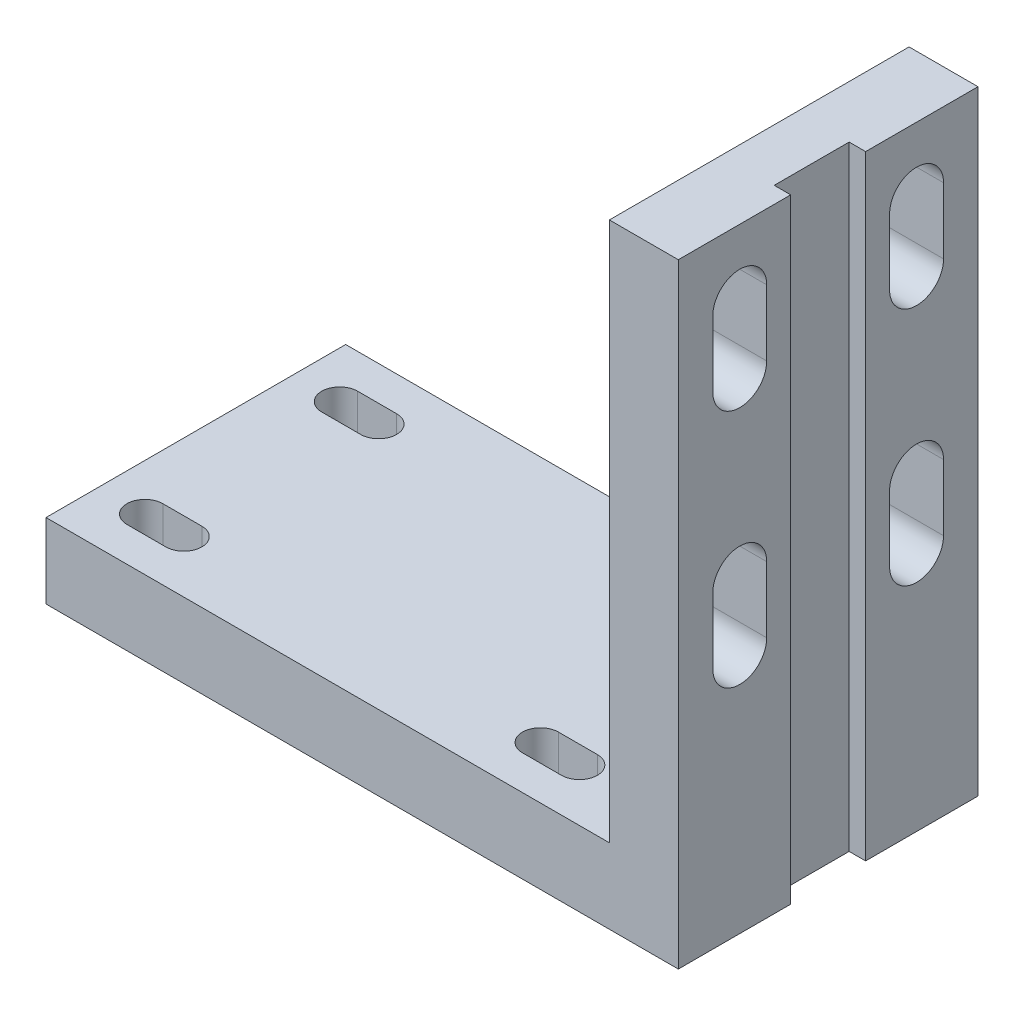
SolidWorks part; units mm, degrees
ref_plane "前视基准面" through (0, 0, 0) normal (0, 0, 1) x (1, 0, 0)
ref_plane "上视基准面" through (0, 0, 0) normal (0, 1, 0) x (1, 0, 0)
ref_plane "右视基准面" through (0, 0, 0) normal (1, 0, 0) x (0, 0, -1)
sketch "草图1" plane through (0, 0, 0) normal (0, 0, 1) x (1, 0, 0)
  line L0 (0, 0) -> (0, -205)
  line L1 (0, -205) -> (-23, -205)
  line L2 (-23, -205) -> (-23, 0)
  line L3 (-23, 0) -> (0, 0)
  dimension "D1" = 205
  dimension "D2" = 23
extrude "凸台-拉伸1" add sketch "草图1" along normal blind 100
sketch "草图3" plane through (0, 0, 100) normal (0, 0, 1) x (1, 0, 0)
  line L0 (-23, -205) -> (-211, -205)
  line L1 (-211, -205) -> (-211, -180)
  line L2 (-211, -180) -> (-23, -180)
  line L3 (-23, 0) -> (-23, -205) construction
  line L4 (-23, -180) -> (-23, -205)
  line L5 (0, -205) -> (0, 0) construction
  dimension "D1" = 211
  dimension "D2" = 25
extrude "凸台-拉伸3" add sketch "草图3" against normal blind 100
sketch "草图4" plane through (0, 0, 0) normal (1, 0, 0) x (0, 0, -1)
  line L0 (-50, 0) -> (-50, -205) construction
  line L1 (-100, 0) -> (0, 0) construction
  line L2 (-100, -205) -> (0, -205) construction
  line L3 (-79.5, -22) -> (-79.5, -44) construction
  line L4 (-70.5, -22) -> (-70.5, -44)
  line L5 (-88.5, -22) -> (-88.5, -44)
  line L6 (-20.5, -22) -> (-20.5, -44) construction
  line L7 (-11.5, -22) -> (-11.5, -44)
  line L8 (-29.5, -22) -> (-29.5, -44)
  line L9 (-79.5, -102) -> (-79.5, -124) construction
  line L10 (-70.5, -102) -> (-70.5, -124)
  line L11 (-88.5, -102) -> (-88.5, -124)
  line L12 (-20.5, -102) -> (-20.5, -124) construction
  line L13 (-11.5, -102) -> (-11.5, -124)
  line L14 (-29.5, -102) -> (-29.5, -124)
  arc A0 (-70.5, -22) -> (-88.5, -22) centre (-79.5, -22) ccw
  arc A1 (-88.5, -44) -> (-70.5, -44) centre (-79.5, -44) ccw
  arc A2 (-11.5, -22) -> (-29.5, -22) centre (-20.5, -22) ccw
  arc A3 (-29.5, -44) -> (-11.5, -44) centre (-20.5, -44) ccw
  arc A4 (-70.5, -102) -> (-88.5, -102) centre (-79.5, -102) ccw
  arc A5 (-88.5, -124) -> (-70.5, -124) centre (-79.5, -124) ccw
  arc A6 (-11.5, -102) -> (-29.5, -102) centre (-20.5, -102) ccw
  arc A7 (-29.5, -124) -> (-11.5, -124) centre (-20.5, -124) ccw
  point P8 (-79.5, -33)
  point P13 (-20.5, -33)
  point P20 (-79.5, -113)
  point P27 (-20.5, -113)
  point P35 (-88.5, -33)
  dimension "D2" = 13
  dimension "D3" = 40
  dimension "D4" = 80
  dimension "D1" = 59
  dimension "D5" = 18
extrude "切除-拉伸1" cut sketch "草图4" against normal up to next
sketch "草图5" plane through (0, -205, 0) normal (0, -1, 0) x (1, 0, 0)
  line L0 (-211, 50) -> (0, 50) construction
  line L1 (-211, 0) -> (-211, 100) construction
  line L2 (0, 100) -> (0, 0) construction
  line L3 (-195.5, 82.5) -> (-182.5, 82.5) construction
  line L4 (-195.5, 88.5) -> (-182.5, 88.5)
  line L5 (-195.5, 76.5) -> (-182.5, 76.5)
  line L6 (-63.5, 82.5) -> (-50.5, 82.5) construction
  line L7 (-63.5, 88.5) -> (-50.5, 88.5)
  line L8 (-63.5, 76.5) -> (-50.5, 76.5)
  line L9 (-195.5, 17.5) -> (-182.5, 17.5) construction
  line L10 (-195.5, 23.5) -> (-182.5, 23.5)
  line L11 (-195.5, 11.5) -> (-182.5, 11.5)
  line L12 (-63.5, 17.5) -> (-50.5, 17.5) construction
  line L13 (-63.5, 23.5) -> (-50.5, 23.5)
  line L14 (-63.5, 11.5) -> (-50.5, 11.5)
  arc A0 (-195.5, 88.5) -> (-195.5, 76.5) centre (-195.5, 82.5) ccw
  arc A1 (-182.5, 76.5) -> (-182.5, 88.5) centre (-182.5, 82.5) ccw
  arc A2 (-63.5, 88.5) -> (-63.5, 76.5) centre (-63.5, 82.5) ccw
  arc A3 (-50.5, 76.5) -> (-50.5, 88.5) centre (-50.5, 82.5) ccw
  arc A4 (-195.5, 23.5) -> (-195.5, 11.5) centre (-195.5, 17.5) ccw
  arc A5 (-182.5, 11.5) -> (-182.5, 23.5) centre (-182.5, 17.5) ccw
  arc A6 (-63.5, 23.5) -> (-63.5, 11.5) centre (-63.5, 17.5) ccw
  arc A7 (-50.5, 11.5) -> (-50.5, 23.5) centre (-50.5, 17.5) ccw
  point P8 (-189, 82.5)
  point P13 (-57, 82.5)
  point P20 (-189, 17.5)
  point P27 (-57, 17.5)
  dimension "D2" = 25
  dimension "D4" = 132
  dimension "D1" = 9.5
  dimension "D3" = 65
  dimension "D5" = 12
extrude "切除-拉伸2" cut sketch "草图5" against normal up to next
sketch "草图6" plane through (0, 0, 0) normal (1, 0, 0) x (0, 0, -1)
  line L0 (-50, 0) -> (-50, -205) construction
  line L1 (-100, 0) -> (0, 0) construction
  line L2 (-100, -205) -> (0, -205) construction
  line L3 (-62.5, 0) -> (-62.5, -205)
  line L4 (-37.5, 0) -> (-37.5, -205)
  line L5 (-62.5, 0) -> (-37.5, 0)
  line L6 (-37.5, -205) -> (-62.5, -205)
  dimension "D1" = 12.5
  dimension "D2" = 12.5
extrude "切除-拉伸3" cut sketch "草图6" against normal blind 5.5
